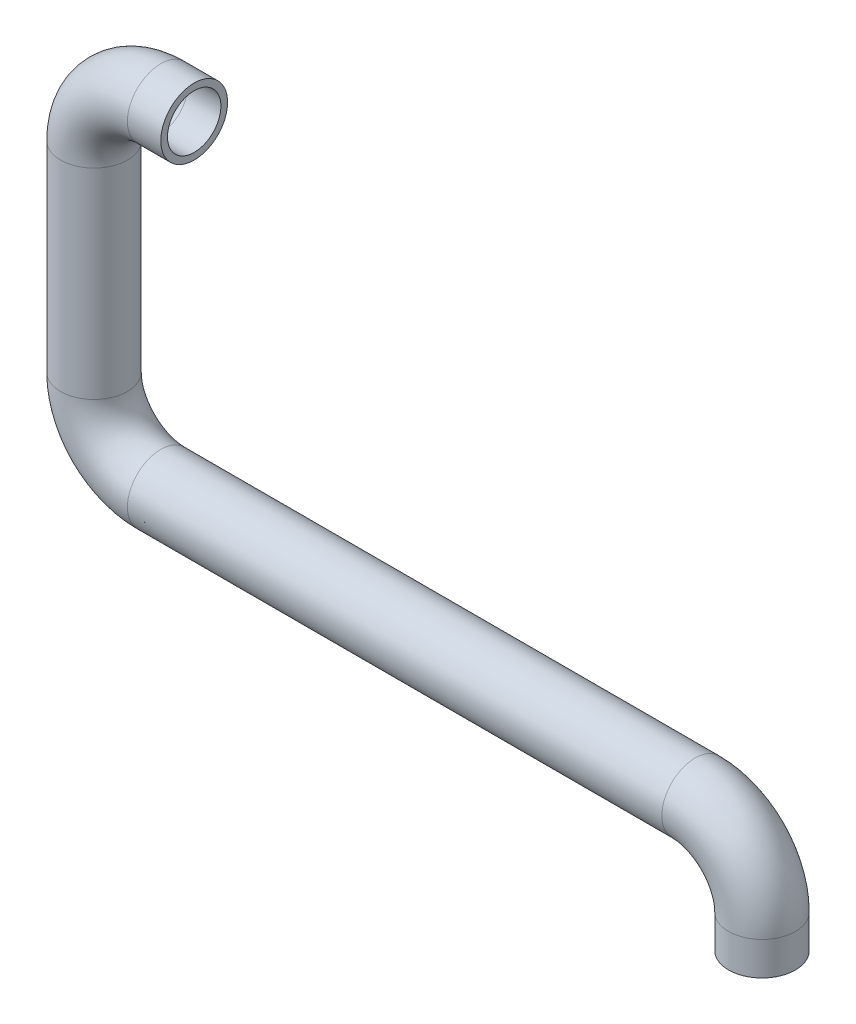
SolidWorks part; units mm, degrees
ref_plane "前视基准面" through (0, 0, 0) normal (0, 0, 1) x (1, 0, 0)
ref_plane "上视基准面" through (0, 0, 0) normal (0, 1, 0) x (1, 0, 0)
ref_plane "右视基准面" through (0, 0, 0) normal (1, 0, 0) x (0, 0, -1)
other "Configuration Table"
sketch "草图1" plane through (0, 0, 0) normal (0, 0, 1) x (1, 0, 0)
  line L0 (-10, 0) -> (-90, 0)
  line L1 (-100, 10) -> (-100, 40)
  line L2 (-90, 50) -> (-85, 50)
  line L3 (0, -10) -> (0, -15)
  arc A0 (-90, 0) -> (-100, 10) centre (-90, 10) cw
  arc A1 (-100, 40) -> (-90, 50) centre (-90, 40) cw
  arc A2 (-10, 0) -> (0, -10) centre (-10, -10) cw
  point P8 (-100, 0)
  point P11 (-100, 50)
  point P14 (0, 0)
  dimension "D5" = 10
  dimension "D6" = 10
  dimension "D1" = 15
  dimension "D2" = 100
  dimension "D3" = 50
  dimension "D4" = 15
sweep "扫描-薄件1" add path "草图1" circular profile diameter 10 parameters "D1"=1, "D3"=10
